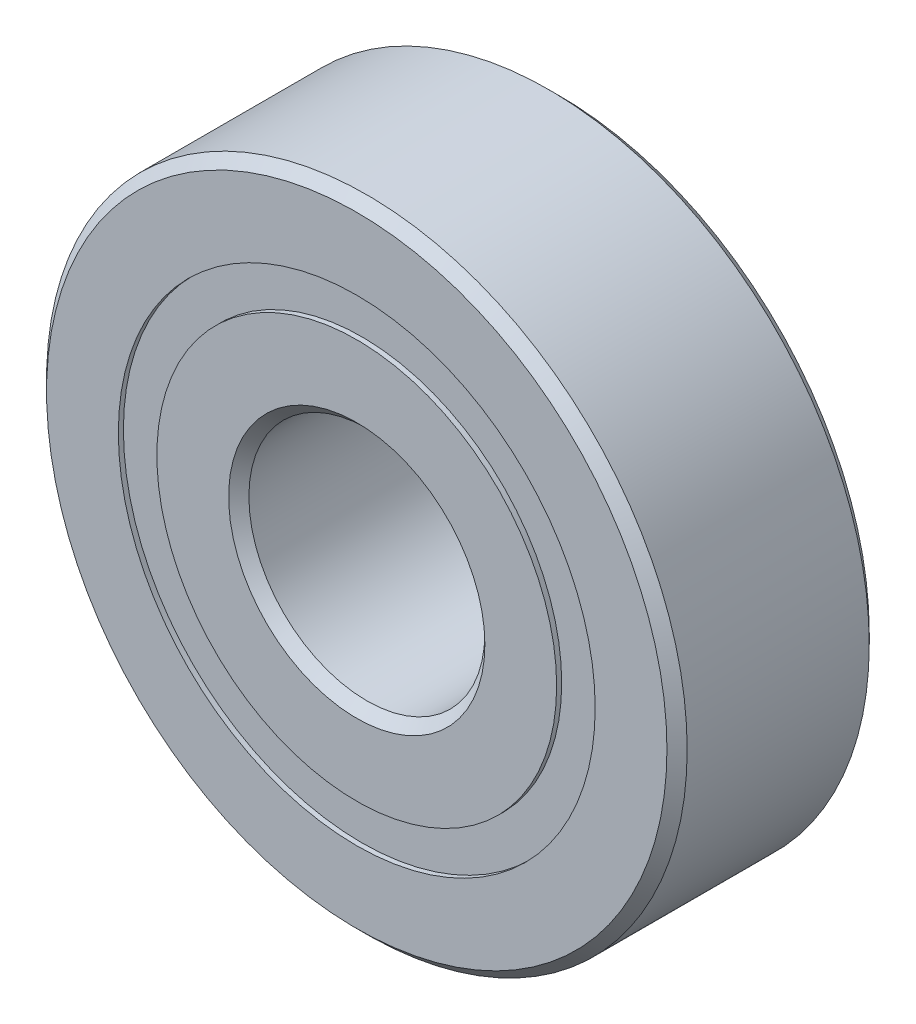
SolidWorks part; units mm, degrees
ref_plane "Front Plane" through (0, 0, 0) normal (0, 0, 1) x (1, 0, 0)
ref_plane "Top Plane" through (0, 0, 0) normal (0, 1, 0) x (1, 0, 0)
ref_plane "Right Plane" through (0, 0, 0) normal (1, 0, 0) x (0, 0, -1)
sketch "Sketch1" plane through (0, 0, 0) normal (0, 0, 1) x (1, 0, 0)
  circle A0 centre (0, 0) radius 9.5 construction
  circle A1 centre (0, 0) radius 3.5 construction
  dimension "OD" = 19
  dimension "Shaft Dia" = 7
sketch "Sketch2" plane through (0, 0, 0) normal (1, 0, 0) x (0, 0, -1)
  line L0 (-3, 0) -> (3, 0) construction
  line L1 (0, 9.5) -> (0, -9.5) construction
  line L2 (2.7, 9.5) -> (-2.7, 9.5) construction
  line L3 (-2.7, 9.5) -> (-3, 9.2) construction
  line L4 (-3, 9.2) -> (-3, 7.0714) construction
  line L5 (-3, 7.0714) -> (-1.3333, 7.0714) construction
  line L6 (3, 7.0714) -> (1.3333, 7.0714) construction
  line L7 (3, 9.2) -> (3, 7.0714) construction
  line L8 (2.7, 9.5) -> (3, 9.2) construction
  line L9 (0, 9.5) -> (0, 6.5) construction
  line L10 (0, 6.5) -> (0, 3.5) construction
  line L11 (3, 6.5) -> (-3, 6.5) construction
  line L12 (-3, 3.8) -> (-3, 5.9286) construction
  line L13 (-2.7, 3.5) -> (-3, 3.8) construction
  line L14 (2.7, 3.5) -> (-2.7, 3.5) construction
  line L15 (2.7, 3.5) -> (3, 3.8) construction
  line L16 (3, 3.8) -> (3, 5.9286) construction
  line L17 (3, 5.9286) -> (1.3333, 5.9286) construction
  line L18 (-3, 5.9286) -> (-1.3333, 5.9286) construction
  arc A0 (-1.3333, 7.0714) -> (1.3333, 7.0714) centre (0, 6.5) cw construction
  arc A1 (-1.3333, 5.9286) -> (1.3333, 5.9286) centre (0, 6.5) ccw construction
  point P14 (0, 3.5)
  point P18 (0, 6.5)
  dimension "D1" = 45
  dimension "D2" = 0.3
  dimension "D3" = 2.6667
  dimension "D4" = 0.5714
  dimension "Width" = 6
sketch "Sketch6" plane through (0, 0, 0) normal (1, 0, 0) x (0, 0, -1)
  line L0 (-3, 9.2) -> (-3, 7.0714) construction
  line L1 (-2.7, 9.5) -> (-3, 9.2) construction
  line L2 (2.7, 9.5) -> (-2.7, 9.5) construction
  line L3 (2.7, 9.5) -> (3, 9.2) construction
  line L4 (3, 9.2) -> (3, 7.0714) construction
  line L5 (3, 7.0714) -> (1.3333, 7.0714) construction
  line L6 (-3, 7.0714) -> (-1.3333, 7.0714) construction
  line L7 (-3, 9.2) -> (-3, 7.0714)
  line L8 (-2.7, 9.5) -> (-3, 9.2)
  line L9 (2.7, 9.5) -> (-2.7, 9.5)
  line L10 (2.7, 9.5) -> (3, 9.2)
  line L11 (3, 9.2) -> (3, 7.0714)
  line L12 (3, 7.0714) -> (1.3333, 7.0714)
  line L13 (-3, 7.0714) -> (-1.3333, 7.0714)
  line L14 (-3, 3.8) -> (-3, 5.9286) construction
  line L15 (-2.7, 3.5) -> (-3, 3.8) construction
  line L16 (2.7, 3.5) -> (-2.7, 3.5) construction
  line L17 (2.7, 3.5) -> (3, 3.8) construction
  line L18 (3, 3.8) -> (3, 5.9286) construction
  line L19 (3, 5.9286) -> (1.3333, 5.9286) construction
  line L20 (-3, 5.9286) -> (-1.3333, 5.9286) construction
  line L21 (-3, 3.8) -> (-3, 5.9286)
  line L22 (-2.7, 3.5) -> (-3, 3.8)
  line L23 (2.7, 3.5) -> (-2.7, 3.5)
  line L24 (2.7, 3.5) -> (3, 3.8)
  line L25 (3, 3.8) -> (3, 5.9286)
  line L26 (3, 5.9286) -> (1.3333, 5.9286)
  line L27 (-3, 5.9286) -> (-1.3333, 5.9286)
  arc A0 (1.3333, 7.0714) -> (-1.3333, 7.0714) centre (0, 6.5) ccw construction
  arc A1 (1.3333, 7.0714) -> (-1.3333, 7.0714) centre (0, 6.5) ccw
  arc A2 (-1.3333, 5.9286) -> (1.3333, 5.9286) centre (0, 6.5) ccw construction
  arc A3 (-1.3333, 5.9286) -> (1.3333, 5.9286) centre (0, 6.5) ccw
revolve "Revolve1" add sketch "Sketch6" angle 360 about L0
sketch "Sketch4" plane through (0, 0, 0) normal (1, 0, 0) x (0, 0, -1)
  line L0 (-1.4506, 6.5) -> (1.4506, 6.5)
  arc A2 (-1.4506, 6.5) -> (1.4506, 6.5) centre (0, 6.5) cw
  arc A3 (1.3333, 7.0714) -> (-1.3333, 7.0714) centre (0, 6.5) ccw construction
revolve "Revolve2" add sketch "Sketch4" angle 360 about L0
ref_axis "Axis1" through (0, 0, -3) along (0, 0, 1)
pattern_circular "CirPattern1" count 12 every 30 about axis through (0, 0, -3) along (0, 0, 1) of bodies 104
sketch "Sketch5" plane through (0, 0, 0) normal (1, 0, 0) x (0, 0, -1)
  line L0 (-3, 7.0714) -> (-1.3333, 7.0714) construction
  line L1 (-2.85, 7.0714) -> (-1.4506, 7.0714)
  line L2 (-2.85, 7.0714) -> (-2.85, 5.9286)
  line L3 (-2.85, 5.9286) -> (-1.4506, 5.9286)
  line L4 (-1.4506, 7.0714) -> (-1.4506, 5.9286)
  line L6 (3, 7.0714) -> (1.3333, 7.0714) construction
  line L7 (2.85, 7.0714) -> (1.4506, 7.0714)
  line L8 (2.85, 7.0714) -> (2.85, 5.9286)
  line L9 (2.85, 5.9286) -> (1.4506, 5.9286)
  line L10 (1.4506, 7.0714) -> (1.4506, 5.9286)
  line L12 (-2.7, 9.5) -> (-3, 9.2) construction
  line L13 (-3, 5.9286) -> (-1.3333, 5.9286) construction
  line L14 (3, 5.9286) -> (1.3333, 5.9286) construction
  point P18 (-2.85, 9.35)
revolve "Revolve3" add sketch "Sketch5" angle 360 about L0
equation "\"D2@Sketch2\"= \"Width@Sketch2\" * .05"
equation "\"D3@Sketch2\"=\"Width@Sketch2\" / 2.25"
equation "\"D4@Sketch2\"= ( ( ( \"OD@Sketch1\" - \"Width@Sketch2\" ) / 2 ) / 3.25 ) / 3.5"
equation "\"D2@CirPattern1\" = 360/\"Balls@CirPattern1\""
